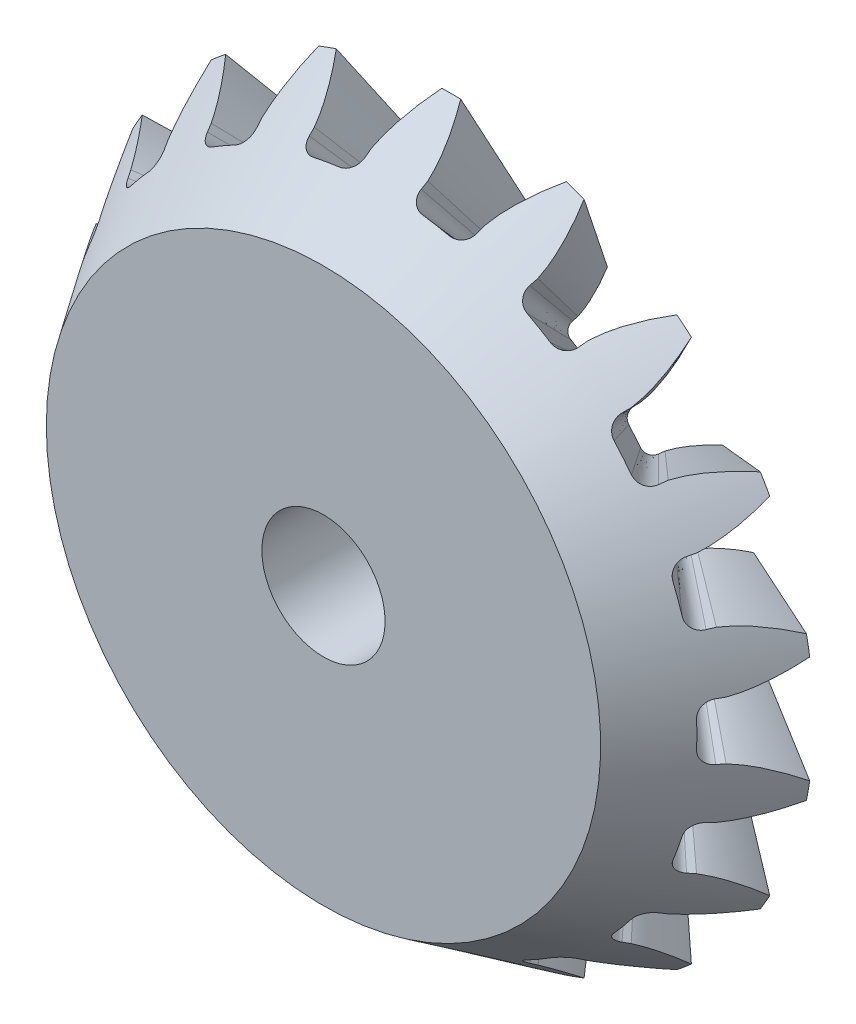
SolidWorks part; units mm, degrees
ref_plane "Front Plane" through (0, 0, 0) normal (0, 0, 1) x (1, 0, 0)
ref_plane "Top Plane" through (0, 0, 0) normal (0, 1, 0) x (1, 0, 0)
ref_plane "Right Plane" through (0, 0, 0) normal (1, 0, 0) x (0, 0, -1)
ref_axis "Gear Axis" through (0, 0, -1.3521) along (0, 0, 1)
sketch "Blank Sketch" plane through (0, 0, 0) normal (0, 1, 0) x (1, 0, 0)
  line L0 (0, 0) -> (0, -27.0416) construction
  line L1 (0, 0) -> (22.5, -15) construction
  line L2 (0, 0) -> (15.0115, -10.0077) construction
  line L3 (11.176, -15.7611) -> (15.6135, -9.1047)
  line L4 (15.6135, -9.1047) -> (23.5324, -13.4515)
  line L5 (23.5324, -13.4515) -> (17.9981, -21.7528)
  line L6 (17.9981, -21.7528) -> (4, -21.7528)
  line L7 (4, -21.7528) -> (4, -15.7611)
  line L8 (4, -15.7611) -> (11.176, -15.7611)
  line L9 (22.5, -15) -> (23.5324, -13.4515) construction
  line L10 (22.5, -15) -> (17.9981, -21.7528) construction
  line L11 (15.0115, -10.0077) -> (11.176, -15.7611) construction
  dimension "Axis" = 27.0416
  dimension "Cone" = 56.31
  dimension "Heel" = 27.0416
  dimension "Toe Cone" = 56.31
  dimension "Toe" = 18.0416
  dimension "Heel Square" = 90
  dimension "Addendum" = 1.8611
  dimension "Root Square" = 90
  dimension "Heel Rim" = 8.1158
  dimension "Toe Square" = 90
  dimension "Toe Rim" = 6.9147
  dimension "Front Square" = 90
  dimension "Face" = 4.927
  dimension "Back" = 13.9981
  dimension "Front" = 7.176
revolve "Blank" add sketch "Blank Sketch" angle 360 about L0
sketch "Cone Sketch" plane through (0, 0, 0) normal (0, 1, 0) x (1, 0, 0)
  line L0 (0, 0) -> (0, -27.0416) construction
  line L1 (0, 0) -> (24.5801, -16.3868)
  line L2 (0, 0) -> (12.9314, -8.6209)
  dimension "Axis" = 27.0416
  dimension "Toe Cone" = 56.31
  dimension "Heel Cone" = 56.31
  dimension "Heel" = 29.5416
  dimension "Toe" = 15.5416
ref_plane "Heel Plane" through (24.5801, 0, 16.3868) normal (0.8321, 0, 0.5547) x (0.5547, 0, -0.8321)
ref_plane "Toe Plane" through (12.9314, 0, 8.6209) normal (0.8321, 0, 0.5547) x (0.5547, 0, -0.8321)
sketch "Heel Section Sketch" plane through (24.5801, 0, 16.3868) normal (0.8321, 0, 0.5547) x (0.5547, 0, -0.8321)
  line L0 (0, 0) -> (-44.3125, 0) construction
  line L1 (-2.4361, 2.0543) -> (-2.9674, 2.0282)
  line L2 (-2.4361, -2.0543) -> (-2.9674, -2.0282)
  line L3 (4.4427, 5.6087) -> (4.4427, -5.6087)
  arc A0 (-2.9674, 2.0282) -> (-3.9541, 0.9668) centre (-2.9166, 0.9916) ccw
  arc A1 (-3.9541, -0.9668) -> (-2.9674, -2.0282) centre (-2.9166, -0.9916) ccw
  arc A2 (-3.9541, -0.9668) -> (-3.9541, 0.9668) centre (-44.3125, 0) ccw
  spline S0 degree 4 poles (-2.6291, 2.0265) (-2.5842, 2.0316) (-2.4741, 2.0474) (-2.3933, 2.0609) (-2.1776, 2.1023) (-2.0149, 2.1404) (-1.7927, 2.1952) (-1.5783, 2.2566) (-1.3413, 2.3286) (-1.1153, 2.4041) (-0.8853, 2.4853) (-0.6604, 2.5702) (-0.4261, 2.6632) (-0.1395, 2.7831) (0.2014, 2.935) (0.5903, 3.1201) (1.0229, 3.342) (1.4443, 3.5713) (1.8678, 3.8174) (2.2724, 4.0631) (2.6924, 4.335) (3.0718, 4.5879) (3.5028, 4.8948) (3.8332, 5.1342) (4.292, 5.4883) (4.5055, 5.6577) (4.7688, 5.8719) (4.9185, 5.9962) (4.989, 6.0556) (5.0278, 6.0882) (5.0475, 6.1048) knots 0 0 0 0 0 0.022117 0.039787 0.058126 0.081614 0.109122 0.13663 0.164138 0.191645 0.219153 0.246661 0.274169 0.305931 0.360947 0.415962 0.470978 0.525993 0.581009 0.636024 0.69104 0.746055 0.801071 0.856086 0.911102 0.955551 0.977775 0.988888 1 1 1 1 1 construction
  spline S1 degree 4 poles (-2.4361, 2.0543) (-2.4021, 2.06) (-2.3349, 2.0721) (-2.1776, 2.1023) (-2.0149, 2.1404) (-1.7927, 2.1952) (-1.5783, 2.2566) (-1.3413, 2.3286) (-1.1153, 2.4041) (-0.8853, 2.4853) (-0.6604, 2.5702) (-0.4261, 2.6632) (-0.1395, 2.7831) (0.2014, 2.935) (0.5903, 3.1201) (1.0229, 3.342) (1.4443, 3.5713) (1.8678, 3.8174) (2.2724, 4.0631) (2.6924, 4.335) (3.0718, 4.5879) (3.5028, 4.8948) (3.8332, 5.1342) (4.1946, 5.4131) (4.3587, 5.5418) (4.4427, 5.6087) knots 0.022117 0.022117 0.022117 0.022117 0.022117 0.039787 0.058126 0.081614 0.109122 0.13663 0.164138 0.191645 0.219153 0.246661 0.274169 0.305931 0.360947 0.415962 0.470978 0.525993 0.581009 0.636024 0.69104 0.746055 0.801071 0.856086 0.911102 0.911102 0.911102 0.911102 0.911102
  spline S2 degree 4 poles (-2.6291, -2.0265) (-2.5842, -2.0316) (-2.4741, -2.0474) (-2.3933, -2.0609) (-2.1776, -2.1023) (-2.0149, -2.1404) (-1.7927, -2.1952) (-1.5783, -2.2566) (-1.3413, -2.3286) (-1.1153, -2.4041) (-0.8853, -2.4853) (-0.6604, -2.5702) (-0.4261, -2.6632) (-0.1395, -2.7831) (0.2014, -2.935) (0.5903, -3.1201) (1.0229, -3.342) (1.4443, -3.5713) (1.8678, -3.8174) (2.2724, -4.0631) (2.6924, -4.335) (3.0718, -4.5879) (3.5028, -4.8948) (3.8332, -5.1342) (4.292, -5.4883) (4.5055, -5.6577) (4.7688, -5.8719) (4.9185, -5.9962) (4.989, -6.0556) (5.0278, -6.0882) (5.0475, -6.1048) knots 0 0 0 0 0 0.022117 0.039787 0.058126 0.081614 0.109122 0.13663 0.164138 0.191645 0.219153 0.246661 0.274169 0.305931 0.360947 0.415962 0.470978 0.525993 0.581009 0.636024 0.69104 0.746055 0.801071 0.856086 0.911102 0.955551 0.977775 0.988888 1 1 1 1 1 construction
  spline S3 degree 4 poles (-2.4361, -2.0543) (-2.4021, -2.06) (-2.3349, -2.0721) (-2.1776, -2.1023) (-2.0149, -2.1404) (-1.7927, -2.1952) (-1.5783, -2.2566) (-1.3413, -2.3286) (-1.1153, -2.4041) (-0.8853, -2.4853) (-0.6604, -2.5702) (-0.4261, -2.6632) (-0.1395, -2.7831) (0.2014, -2.935) (0.5903, -3.1201) (1.0229, -3.342) (1.4443, -3.5713) (1.8678, -3.8174) (2.2724, -4.0631) (2.6924, -4.335) (3.0718, -4.5879) (3.5028, -4.8948) (3.8332, -5.1342) (4.1946, -5.4131) (4.3587, -5.5418) (4.4427, -5.6087) knots 0.022117 0.022117 0.022117 0.022117 0.022117 0.039787 0.058126 0.081614 0.109122 0.13663 0.164138 0.191645 0.219153 0.246661 0.274169 0.305931 0.360947 0.415962 0.470978 0.525993 0.581009 0.636024 0.69104 0.746055 0.801071 0.856086 0.911102 0.911102 0.911102 0.911102 0.911102
  dimension "Root" = 40.3699
  dimension "Fillet" = 1.0378
  dimension "Centre" = 44.3125
sketch "Toe Section Sketch" plane through (12.9314, 0, 8.6209) normal (0.8321, 0, 0.5547) x (0.5547, 0, -0.8321)
  line L0 (0, 0) -> (-23.3125, 0) construction
  line L1 (-1.2816, 1.0807) -> (-1.5611, 1.067)
  line L2 (-1.2816, -1.0807) -> (-1.5611, -1.067)
  line L3 (2.3373, 2.9507) -> (2.3373, -2.9507)
  arc A0 (-1.5611, 1.067) -> (-2.0802, 0.5086) centre (-1.5344, 0.5217) ccw
  arc A1 (-2.0802, -0.5086) -> (-1.5611, -1.067) centre (-1.5344, -0.5217) ccw
  arc A2 (-2.0802, -0.5086) -> (-2.0802, 0.5086) centre (-23.3125, 0) ccw
  spline S0 degree 4 poles (-1.3857, 1.0656) (-1.3554, 1.0695) (-1.3037, 1.0768) (-1.2572, 1.0845) (-1.1474, 1.1057) (-1.0584, 1.1263) (-0.9443, 1.1547) (-0.8296, 1.1873) (-0.7061, 1.225) (-0.5865, 1.2648) (-0.4659, 1.3075) (-0.3473, 1.3522) (-0.2242, 1.4011) (-0.0733, 1.4642) (0.1059, 1.5441) (0.3106, 1.6415) (0.5381, 1.7582) (0.7598, 1.8788) (0.9826, 2.0083) (1.1955, 2.1376) (1.4164, 2.2806) (1.6161, 2.4137) (1.8427, 2.5751) (2.0167, 2.7011) (2.2578, 2.8872) (2.3846, 2.9878) (2.5448, 3.1185) (2.6148, 3.1774) (2.6547, 3.2111) knots 0 0 0 0 0 0.022117 0.039787 0.058126 0.081614 0.109122 0.13663 0.164138 0.191645 0.219153 0.246661 0.274169 0.305931 0.360947 0.415962 0.470978 0.525993 0.581009 0.636024 0.69104 0.746055 0.801071 0.856086 0.911102 0.955551 1 1 1 1 1 construction
  spline S1 degree 4 poles (-1.2816, 1.0807) (-1.2637, 1.0837) (-1.2275, 1.0903) (-1.1474, 1.1057) (-1.0584, 1.1263) (-0.9443, 1.1547) (-0.8296, 1.1873) (-0.7061, 1.225) (-0.5865, 1.2648) (-0.4659, 1.3075) (-0.3473, 1.3522) (-0.2242, 1.4011) (-0.0733, 1.4642) (0.1059, 1.5441) (0.3106, 1.6415) (0.5381, 1.7582) (0.7598, 1.8788) (0.9826, 2.0083) (1.1955, 2.1376) (1.4164, 2.2806) (1.6161, 2.4137) (1.8427, 2.5751) (2.0167, 2.7011) (2.2067, 2.8477) (2.2931, 2.9155) (2.3373, 2.9507) knots 0.022117 0.022117 0.022117 0.022117 0.022117 0.039787 0.058126 0.081614 0.109122 0.13663 0.164138 0.191645 0.219153 0.246661 0.274169 0.305931 0.360947 0.415962 0.470978 0.525993 0.581009 0.636024 0.69104 0.746055 0.801071 0.856086 0.911102 0.911102 0.911102 0.911102 0.911102
  spline S2 degree 4 poles (-1.3857, -1.0656) (-1.3554, -1.0695) (-1.3037, -1.0768) (-1.2572, -1.0845) (-1.1474, -1.1057) (-1.0584, -1.1263) (-0.9443, -1.1547) (-0.8296, -1.1873) (-0.7061, -1.225) (-0.5865, -1.2648) (-0.4659, -1.3075) (-0.3473, -1.3522) (-0.2242, -1.4011) (-0.0733, -1.4642) (0.1059, -1.5441) (0.3106, -1.6415) (0.5381, -1.7582) (0.7598, -1.8788) (0.9826, -2.0083) (1.1955, -2.1376) (1.4164, -2.2806) (1.6161, -2.4137) (1.8427, -2.5751) (2.0167, -2.7011) (2.2578, -2.8872) (2.3846, -2.9878) (2.5448, -3.1185) (2.6148, -3.1774) (2.6547, -3.2111) knots 0 0 0 0 0 0.022117 0.039787 0.058126 0.081614 0.109122 0.13663 0.164138 0.191645 0.219153 0.246661 0.274169 0.305931 0.360947 0.415962 0.470978 0.525993 0.581009 0.636024 0.69104 0.746055 0.801071 0.856086 0.911102 0.955551 1 1 1 1 1 construction
  spline S3 degree 4 poles (-1.2816, -1.0807) (-1.2637, -1.0837) (-1.2275, -1.0903) (-1.1474, -1.1057) (-1.0584, -1.1263) (-0.9443, -1.1547) (-0.8296, -1.1873) (-0.7061, -1.225) (-0.5865, -1.2648) (-0.4659, -1.3075) (-0.3473, -1.3522) (-0.2242, -1.4011) (-0.0733, -1.4642) (0.1059, -1.5441) (0.3106, -1.6415) (0.5381, -1.7582) (0.7598, -1.8788) (0.9826, -2.0083) (1.1955, -2.1376) (1.4164, -2.2806) (1.6161, -2.4137) (1.8427, -2.5751) (2.0167, -2.7011) (2.2067, -2.8477) (2.2931, -2.9155) (2.3373, -2.9507) knots 0.022117 0.022117 0.022117 0.022117 0.022117 0.039787 0.058126 0.081614 0.109122 0.13663 0.164138 0.191645 0.219153 0.246661 0.274169 0.305931 0.360947 0.415962 0.470978 0.525993 0.581009 0.636024 0.69104 0.746055 0.801071 0.856086 0.911102 0.911102 0.911102 0.911102 0.911102
  dimension "Root" = 21.2383
  dimension "Fillet" = 0.546
  dimension "Centre" = 23.3125
loft "Tooth Space" cut profiles "Heel Section Sketch", "Toe Section Sketch"
pattern_circular "Teeth" count 18 over 360 about axis through (0, 0, -1.3521) along (0, 0, 1) of "Tooth Space"
equation "\"No. of Teeth\"= 18"
equation "\"Module\"= 2.5"
equation "\"Bore Diameter\"= 8"
equation "\"Pressure Angle\"= 20"
equation "\"Shaft Angle\"= 90"
equation "\"Mate Teeth\"= 12"
equation "\"Pitch Cone Angle\"= IIF ( ( \"Mate Teeth\" / \"No. of Teeth\" + cos ( \"Shaft Angle\" ) ) > 0 , atn ( sin ( \"Shaft Angle\" ) / ( \"Mate Teeth\" / \"No. of Teeth\" + cos ( \"Shaft Angle\" ) ) ) , 180 + atn ( sin ( \"Shaft Angle\" ) / ( \"Mate Teeth\" / \"No. of Teeth\" + cos ( \"Shaft Angle\" ) ) ) )"
equation "\"Mate Cone Angle\"= \"Shaft Angle\" - \"Pitch Cone Angle\""
equation "\"Addendum\"= IIF ( \"No. of Teeth\" >= \"Mate Teeth\" , 0.54 * \"Module\" + 0.46 * \"Module\" / ( ( \"No. of Teeth\" * cos ( \"Mate Cone Angle\" ) ) / ( \"Mate Teeth\" * cos ( \"Pitch Cone Angle\" ) ) ) , 2 * \"Module\" - ( 0.54 * \"Module\" + 0.46 * \"Module\" / ( ( \"Mate Teeth\" * cos ( \"Pitch Cone Angle\" ) ) / ( \"No. of Teeth\" * cos ( \"Mate Cone Angle\" ) ) ) ) )"
equation "\"Outer Diameter\"= \"No. of Teeth\" * \"Module\" + 2 * \"Addendum\" * cos ( \"Pitch Cone Angle\" )"
equation "\"Pitch Diameter\"= \"No. of Teeth\" * \"Module\""
equation "\"Backlash\"= 0.3 * \"Module\""
equation "\"Arc Length\"= ( ( \"Module\" * pi ) / 2 + \"Backlash\" - 2 * ( \"Addendum\" - \"Module\" ) * tan ( \"Pressure Angle\" ) )"
equation "\"Fillet Radius\"= 0.38 * \"Module\""
equation "\"Mate Addendum\"= 2 * \"Module\" - \"Addendum\""
equation "\"Dedendum\"= 2.188 * \"Module\" - \"Addendum\""
equation "\"Tooth Depth\"= \"Addendum\" + \"Dedendum\""
equation "\"Mate Dedendum\"= 2.188 * \"Module\" - \"Mate Addendum\""
equation "\"Face Width\"= 9"
equation "\"Cone Distance\"= \"Pitch Diameter\" / ( 2 * sin ( \"Pitch Cone Angle\" ) )"
equation "\"Dedendum Angle\"= atn ( \"Dedendum\" / \"Cone Distance\" )"
equation "\"Mate Dedendum Angle\"= atn ( \"Mate Dedendum\" / \"Cone Distance\" )"
equation "\"Face Angle\"= \"Pitch Cone Angle\" + \"Mate Dedendum Angle\""
equation "\"Root Angle\"= \"Pitch Cone Angle\" - \"Dedendum Angle\""
equation "\"Overrun\"= \"Module\""
equation "\"Back Cone Pitch Diameter\"= \"Pitch Diameter\" / cos ( \"Pitch Cone Angle\" )"
equation "\"Back Cone Outer Diameter\"= \"Back Cone Pitch Diameter\" + 2 * \"Addendum\""
equation "\"Root Diameter\"= \"Back Cone Outer Diameter\" - 2 * \"Tooth Depth\""
equation "\"Base Diameter\"= \"Back Cone Pitch Diameter\" * cos ( \"Pressure Angle\" )"
equation "\"Base Radius\"= \"Base Diameter\" / 2"
equation "\"Tooth Thickness\"= \"Module\" * pi - \"Arc Length\""
equation "\"Half Space Angle\"= ( \"Arc Length\" / \"Back Cone Pitch Diameter\" ) * 180 / pi"
equation "\"Involute Fn\"= tan ( \"Pressure Angle\" ) - \"Pressure Angle\" * pi / 180"
equation "\"Flank Offset\"= \"Arc Length\" / \"Back Cone Pitch Diameter\" - \"Involute Fn\""
equation "\"Tip Cap Diameter\"= \"Back Cone Outer Diameter\" + 2 * \"Module\""
equation "\"Flank Start Diameter\"= IIF ( \"Base Diameter\" >= ( \"Root Diameter\" + 3 * \"Fillet Radius\" ) , \"Base Diameter\" , \"Root Diameter\" + 3 * \"Fillet Radius\" )"
equation "\"Involute t1\"= ( abs ( ( \"Flank Start Diameter\" / \"Base Diameter\" ) ^ 2 - 1 ) ) ^ 0.5"
equation "\"Involute t2\"= ( abs ( ( \"Tip Cap Diameter\" / \"Base Diameter\" ) ^ 2 - 1 ) ) ^ 0.5"
equation "\"Flank Arc Radius\"= ( \"Back Cone Pitch Diameter\" / 2 ) * sin ( \"Pressure Angle\" )"
equation "\"Flank Centre Angle\"= \"Half Space Angle\" + \"Pressure Angle\""
equation "\"Heel Distance\"= \"Cone Distance\" + \"Overrun\""
equation "\"Toe Distance\"= \"Cone Distance\" - \"Face Width\" - \"Overrun\""
equation "\"Heel Scale\"= \"Heel Distance\" / \"Cone Distance\""
equation "\"Toe Scale\"= \"Toe Distance\" / \"Cone Distance\""
equation "\"Heel Virtual Radius\"= \"Heel Distance\" * tan ( \"Pitch Cone Angle\" )"
equation "\"Toe Virtual Radius\"= \"Toe Distance\" * tan ( \"Pitch Cone Angle\" )"
equation "\"Axis@Blank Sketch\"= \"Cone Distance\""
equation "\"Cone@Blank Sketch\"= \"Pitch Cone Angle\""
equation "\"Heel@Blank Sketch\"= \"Cone Distance\""
equation "\"Toe Cone@Blank Sketch\"= \"Pitch Cone Angle\""
equation "\"Toe@Blank Sketch\"= \"Cone Distance\" - \"Face Width\""
equation "\"Addendum@Blank Sketch\"= \"Addendum\""
equation "\"Heel Rim@Blank Sketch\"= \"Dedendum\" + \"Module\" / cos ( \"Pitch Cone Angle\" )"
equation "\"Toe Rim@Blank Sketch\"= \"Dedendum\" - \"Face Width\" * tan ( \"Dedendum Angle\" ) + \"Module\" / cos ( \"Pitch Cone Angle\" )"
equation "\"Face@Blank Sketch\"= \"Mate Dedendum Angle\""
equation "\"Back@Blank Sketch\"= \"Cone Distance\" * sin ( \"Pitch Cone Angle\" ) - \"Dedendum\" * cos ( \"Pitch Cone Angle\" ) - \"Module\" - \"Bore Diameter\" / 2"
equation "\"Front@Blank Sketch\"= ( \"Cone Distance\" - \"Face Width\" ) * sin ( \"Pitch Cone Angle\" ) - ( \"Dedendum\" - \"Face Width\" * tan ( \"Dedendum Angle\" ) + \"Module\" / cos ( \"Pitch Cone Angle\" ) ) * cos ( \"Pitch Cone Angle\" ) - \"Bore Diameter\" / 2"
equation "\"Axis@Cone Sketch\"= \"Cone Distance\""
equation "\"Heel Cone@Cone Sketch\"= \"Pitch Cone Angle\""
equation "\"Heel@Cone Sketch\"= \"Heel Distance\""
equation "\"Toe Cone@Cone Sketch\"= \"Pitch Cone Angle\""
equation "\"Toe@Cone Sketch\"= \"Toe Distance\""
equation "\"Centre@Heel Section Sketch\"= \"Heel Virtual Radius\""
equation "\"Root@Heel Section Sketch\"= ( \"Root Diameter\" / 2 ) * \"Heel Scale\""
equation "\"Fillet@Heel Section Sketch\"= ( \"Fillet Radius\" ) * \"Heel Scale\""
equation "\"Centre@Toe Section Sketch\"= \"Toe Virtual Radius\""
equation "\"Root@Toe Section Sketch\"= ( \"Root Diameter\" / 2 ) * \"Toe Scale\""
equation "\"Fillet@Toe Section Sketch\"= ( \"Fillet Radius\" ) * \"Toe Scale\""
equation "\"Count@Teeth\"= \"No. of Teeth\""
